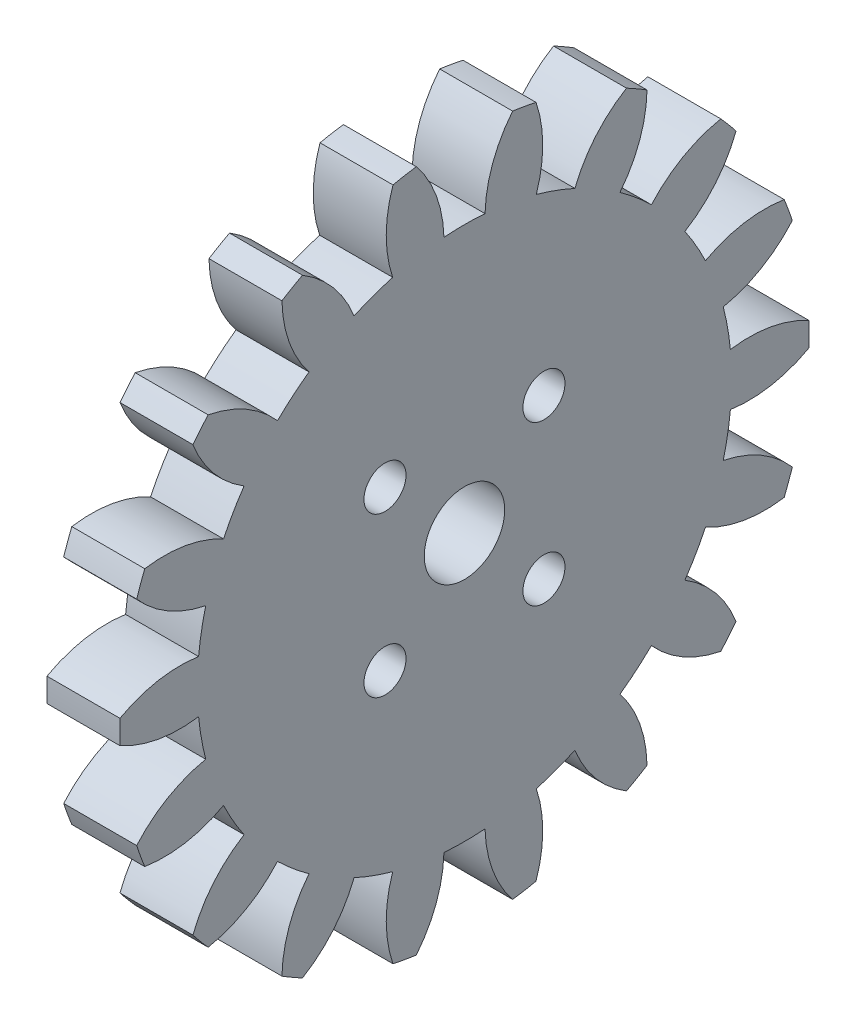
SolidWorks part; units mm, degrees
ref_plane "Plane1" through (0, 0, 0) normal (0, 0, 1) x (1, 0, 0)
ref_plane "Plane2" through (0, 0, 0) normal (0, 1, 0) x (1, 0, 0)
ref_plane "Plane3" through (0, 0, 0) normal (1, 0, 0) x (0, 0, -1)
sketch "HoldingSke" plane through (0, 0, 0) normal (0, 1, 0) x (1, 0, 0)
  line L0 (0, 0) -> (0.317, -0.103)
  line L1 (-15, 0) -> (100, 0) construction
  line L2 (0, 0) -> (-2.1039, 2.3779)
  line L3 (0, 0) -> (-11.863, 4.5341)
  line L4 (0, 0) -> (8.2133, 2.6687)
  line L5 (0, 0) -> (-46.8476, -17.4728)
  line L6 (0, 0) -> (-5.2639, -3.5516)
  line L7 (-2.1039, 2.3779) -> (8.6586, 51.2059)
  line L8 (-76.2, 54.61) -> (-75.2, 54.61)
  line L9 (-67.7845, 28.3722) -> (-49.3413, 33.142)
  line L10 (-76.2, 71.12) -> (104.1128, 71.12)
  line L11 (0, 0) -> (-6.35, 0)
  line L12 (-76.2, 101.6) -> (-76.093, 101.6)
  line L13 (24.9733, 27.94) -> (52.9518, 28.4284)
  line L14 (24.9733, 27.94) -> (24.9743, 27.94)
  line L15 (24.9733, 27.94) -> (100.4006, 29.5858)
  line L16 (-63.627, -3) -> (-12.827, -3)
  circle A0 centre (0, 0) radius 3.5
  circle A1 centre (0, 0) radius 23.249
  circle A2 centre (0, 0) radius 37.5
  circle A3 centre (0, 0) radius 3.5
  dimension "Num_teeth" = 18
  dimension "Pitch_radius" = 180.3128
  dimension "Width" = 6.35
  dimension "Thickness" = 6.35
sketch "BasProSke" plane through (0, 0, 0) normal (0, 1, 0) x (1, 0, 0)
  line L0 (-10, 0) -> (60, 0) construction
  line L1 (0, 0) -> (0, 30)
  line L2 (0, 0) -> (6.35, 0)
  line L3 (6.35, 0) -> (6.35, 30)
  line L4 (6.35, 30) -> (0, 30)
  dimension "Thickness" = 6.35
  dimension "Diameter" = 60
revolve "Base-Revolve" add sketch "BasProSke" angle 360 about L0
sketch "TooCutSke" plane through (0, 0, 0) normal (1, 0, 0) x (0, 0, -1)
  line L1 (0, 0) -> (0, 107) construction
  line L2 (0, 0) -> (-2.5403, 26.8802) construction
  line L3 (0, 0) -> (-9.3468, 53.0082) construction
  line L4 (-2.5403, 26.8802) -> (-4.6734, 26.5041) construction
  arc A0 (1.788, 23.1801) -> (-1.788, 23.1801) centre (0, 0) ccw
  arc A1 (4.2085, 29.729) -> (-4.2085, 29.729) centre (0, 0) ccw
  circle A2 centre (0, 0) radius 27 construction
  circle A3 centre (0, 0) radius 26.14 construction
  arc A4 (-1.788, 23.1801) -> (-4.2085, 29.729) centre (-12.5846, 22.9113) ccw
  arc A5 (4.2085, 29.729) -> (1.788, 23.1801) centre (12.5846, 22.9113) ccw
extrude "ToothCut" cut sketch "TooCutSke" along normal through all
fillet "Breaks" [suppressed] radius 0.06 tangent propagation no
fillet "RootFillets" [suppressed] radius 0.751
pattern_circular "TeethCuts" count 18 every 20 about axis through (-10, 0, 0) along (1, 0, 0) of "ToothCut", "RootFillets", "Breaks"
sketch "HubNeaOneSke" plane through (0, 0, 0) normal (-1, 0, 0) x (0, 0, 1)
  circle A0 centre (0, 0) radius 23.249
  dimension "Diameter" = 46.498
extrude "HubNearOne" [suppressed] add sketch "HubNeaOneSke" along normal blind 43.6501
sketch "HubNeaBotSke" plane through (0, 0, 0) normal (-1, 0, 0) x (0, 0, 1)
  circle A0 centre (0, 0) radius 23.249
  dimension "Diameter" = 46.498
extrude "HubNearBoth" [suppressed] add sketch "HubNeaBotSke" along normal blind 21.825
ref_plane "FarPln" through (6.35, 0, 0) normal (1, 0, 0) x (0, 0, -1)
sketch "HubFarSke" plane through (6.35, 0, 0) normal (1, 0, 0) x (0, 0, -1)
  circle A0 centre (0, 0) radius 23.249
  dimension "Diameter" = 46.498
extrude "HubFar" [suppressed] add sketch "HubFarSke" along normal blind 21.825
sketch "BorSke" plane through (0, 0, 0) normal (1, 0, 0) x (0, 0, -1)
  circle A0 centre (0, 0) radius 3.5
  dimension "Diameter" = 7
extrude "Bore" cut sketch "BorSke" along normal mid plane 100.0001
sketch "KeySke" plane through (0, 0, 0) normal (1, 0, 0) x (0, 0, -1)
  line L0 (-1, 0) -> (-1, 4.5)
  line L1 (-1, 4.5) -> (1, 4.5)
  line L2 (1, 4.5) -> (1, 0)
  line L3 (0, 0) -> (0, 34) construction
  line L4 (-1, 0) -> (1, 0)
  dimension "Width" = 2
extrude "Keyway" [suppressed] cut sketch "KeySke" along normal mid plane 100.0001
pattern_circular "Keyway2" [suppressed] count 2 every 90 about axis through (-10, 0, 0) along (1, 0, 0) reverse direction yes
sketch "Esquisse1" plane through (0, 0, 0) normal (-1, 0, 0) x (0, 0, 1)
  circle A0 centre (-6.9148, 6.9148) radius 1.83
  dimension "D1" = 3.66
extrude "Enlèv. mat.-Extru.1" cut sketch "Esquisse1" against normal up to next
pattern_circular "Répétition circulaire1" count 4 over 360 about axis through (0, 0, 0) along (-1, 0, 0) of "Enlèv. mat.-Extru.1"
equation "' \"Module@HoldingSke\" = 6.35"
equation "' \"Num_teeth@HoldingSke\" = 12"
equation "' \"Ap@HoldingSke\" =  20"
equation "' \"Ap@HoldingSke\" = 20"
equation "' \"Width@HoldingSke\" = 0.5 * 25.4"
equation "' \"Hub_dia@HoldingSke\"= 1 * 25.4"
equation "' \"Hub_dia@HoldingSke\" = 1 * 25.4"
equation "' \"Overall_len@HoldingSke\" = 1.0 * 25.4"
equation "' \"Bore@HoldingSke\" = 0.75 * 25.4"
equation "' \"T_dim@HoldingSke\" = 0.1 * 25.4"
equation "' \"Width@KeySke\" = 0.25 * 25.4"
equation "' \"Show_teeth@HoldingSke\" = 13"
equation "' \"Backlash@HoldingSke\" = 0.009 * 25.4"
equation "' \"Addendum_fac@HoldingSke\" = 1.0"
equation "' \"Dedendum_fac@HoldingSke\" = 1.25"
equation "' \"Dedendum_add@HoldingSke\" = 0.00005 * 25.4"
equation "' \"Clearance_fac@HoldingSke\" = 0.25"
equation "\"Pitch@HoldingSke\" = 1 / \"Module@HoldingSke\""
equation "\"Overcut_dia@TooCutSke\" = (\"Num_teeth@HoldingSke\" + 2 * \"Addendum_fac@HoldingSke\") / \"Pitch@HoldingSke\" + 0.002 * 25.4"
equation "\"Pitch_dia@TooCutSke\" = \"Num_teeth@HoldingSke\" / \"Pitch@HoldingSke\""
equation "\"Base_dia@TooCutSke\" = \"Num_teeth@HoldingSke\" / \"Pitch@HoldingSke\" * cos((\"Ap@HoldingSke\"  * 3.14159265 / 180))"
equation "\"Root_dia@TooCutSke\" = (\"Num_teeth@HoldingSke\" + 2) / \"Pitch@HoldingSke\" - 2 * (\"Addendum_fac@HoldingSke\" + \"Dedendum_fac@HoldingSke\") / \"Pitch@HoldingSke\" - \"Dedendum_add@HoldingSke\" * 2"
equation "\"Half_ang@TooCutSke\" = 180 / \"Num_teeth@HoldingSke\""
equation "\"Half_CT@TooCutSke\" = \"Num_teeth@HoldingSke\" / \"Pitch@HoldingSke\" * sin((3.14159265 / 2 / \"Num_teeth@HoldingSke\")) / 2 - 7 * \"Backlash@HoldingSke\" / 4"
equation "\"Flank_rad@TooCutSke\" = \"Num_teeth@HoldingSke\" / \"Pitch@HoldingSke\" / 5"
equation "\"Radius@RootFillets\" = \"Clearance_fac@HoldingSke\" / \"Pitch@HoldingSke\" + \"Dedendum_add@HoldingSke\""
equation "\"Break_rad@Breaks\" = 0.02 / \"Pitch@HoldingSke\""
equation "\"Thickness@HoldingSke\" = \"Width@HoldingSke\""
equation "\"OAL@HoldingSke\" = \"Thickness@HoldingSke\""
equation "\"MHD@HoldingSke\" = (\"Num_teeth@HoldingSke\" + 2) / \"Pitch@HoldingSke\" - 2 * (\"Addendum_fac@HoldingSke\" + \"Dedendum_fac@HoldingSke\")  / \"Pitch@HoldingSke\" - \"Dedendum_add@HoldingSke\" * 2"
equation "\"MBD@HoldingSke\" = (\"Num_teeth@HoldingSke\" + 2) / \"Pitch@HoldingSke\" - 2 * (\"Addendum_fac@HoldingSke\" + \"Dedendum_fac@HoldingSke\")  / \"Pitch@HoldingSke\" - \"Dedendum_add@HoldingSke\" * 2 - 0.002 * 25.4"
equation "\"MHD@HoldingSke\" = ((sgn( \"MHD@HoldingSke\" - \"Hub_dia@HoldingSke\" )-1)*( \"MHD@HoldingSke\" - \"Hub_dia@HoldingSke\" ))/-2+ \"Hub_dia@HoldingSke\""
equation "\"MBD@HoldingSke\" = ((sgn( \"MBD@HoldingSke\" - \"Bore@HoldingSke\" )-1)*( \"MBD@HoldingSke\" - \"Bore@HoldingSke\" ))/-2+ \"Bore@HoldingSke\""
equation "\"OAL@HoldingSke\" = ((sgn( \"OAL@HoldingSke\" - \"Overall_len@HoldingSke\" )+1)*( \"OAL@HoldingSke\" - \"Overall_len@HoldingSke\" ))/2 + \"Overall_len@HoldingSke\" + 0.000002 * 25.4"
equation "\"Num_teeth@TeethCuts\" = int( \"Show_teeth@HoldingSke\" ) + 1"
equation "\"Num_teeth@TeethCuts\" = ((sgn( \"Num_teeth@TeethCuts\" - \"Num_teeth@HoldingSke\" )-1)*( \"Num_teeth@TeethCuts\" - \"Num_teeth@HoldingSke\" ))/-2+ \"Num_teeth@HoldingSke\""
equation "\"Num_teeth@TeethCuts\" = ((sgn( \"Num_teeth@TeethCuts\" - 2.0)+1)*( \"Num_teeth@TeethCuts\" - 2.0))/2 +2.0"
equation "\"Angle@TeethCuts\" = 360.0 / \"Num_teeth@HoldingSke\""
equation "\"Diameter@BasProSke\" = (\"Num_teeth@HoldingSke\" + 2 * \"Addendum_fac@HoldingSke\") / \"Pitch@HoldingSke\""
equation "\"Thickness@BasProSke\"  = \"Thickness@HoldingSke\""
equation "' \"Fillet_rad@BasProSke\" =  \"Thickness@HoldingSke\" * 0.05"
equation "' \"Fillet_rad@BasProSke\" = \"Thickness@HoldingSke\" * 0.05"
equation "\"MHD@HoldingSke\" = ((sgn( \"MHD@HoldingSke\" - \"Root_dia@TooCutSke\" )-1)*( \"MHD@HoldingSke\" - \"Root_dia@TooCutSke\" ))/-2+ \"Root_dia@TooCutSke\""
equation "\"Diameter@HubNeaOneSke\" = \"MHD@HoldingSke\""
equation "\"Length@HubNearOne\" = \"OAL@HoldingSke\" - \"Thickness@BasProSke\""
equation "\"Diameter@HubNeaBotSke\" = \"MHD@HoldingSke\""
equation "\"Length@HubNearBoth\" = ( \"OAL@HoldingSke\" - \"Thickness@BasProSke\" ) / 2.0"
equation "\"Thickness@FarPln\" = \"Thickness@BasProSke\""
equation "\"Diameter@HubFarSke\" = \"MHD@HoldingSke\""
equation "\"Length@HubFar\" = ( \"OAL@HoldingSke\" - \"Thickness@BasProSke\" ) / 2.0"
equation "\"Diameter@BorSke\" = \"MBD@HoldingSke\""
equation "\"D1@Bore\" = \"OAL@HoldingSke\" * 2.0"
equation "\"D1@Keyway\" = \"OAL@HoldingSke\" * 2.0"
equation "\"Offset@KeySke\" = \"T_dim@HoldingSke\" + \"MBD@HoldingSke\" / 2.0"
